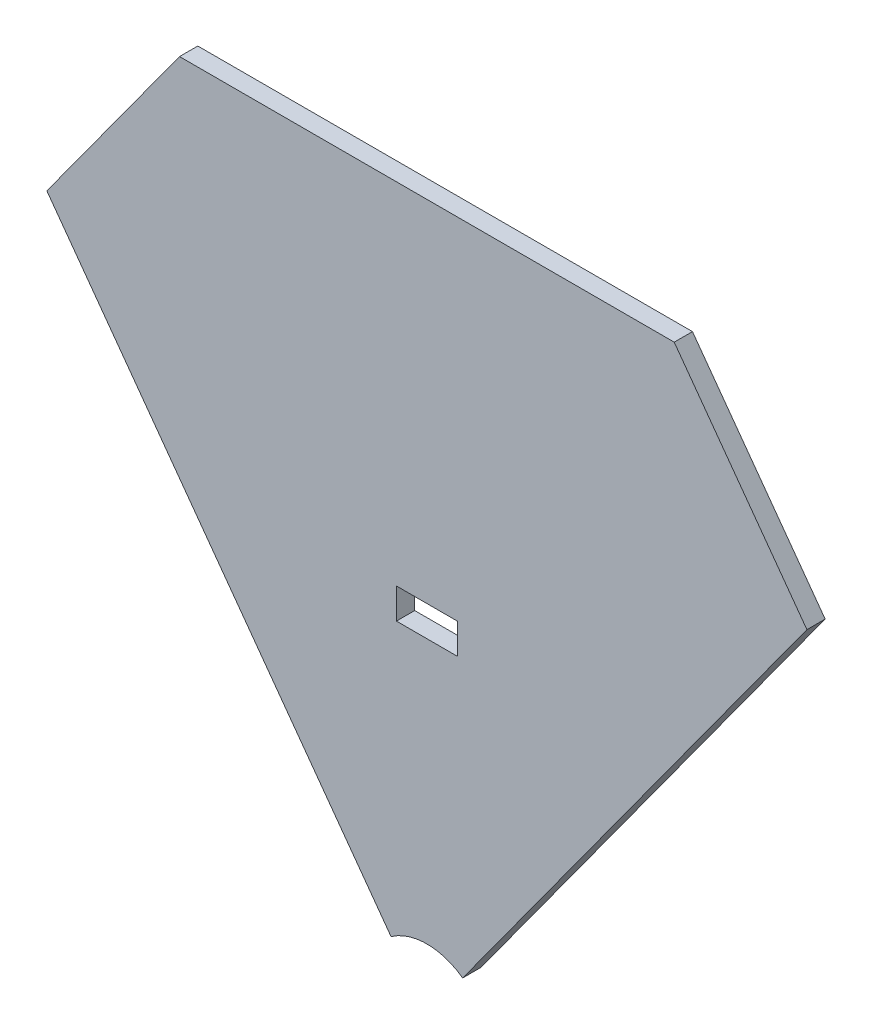
SolidWorks part; units mm, degrees
ref_plane "Front Plane" through (0, 0, 0) normal (0, 0, 1) x (1, 0, 0)
ref_plane "Top Plane" through (0, 0, 0) normal (0, 1, 0) x (1, 0, 0)
ref_plane "Right Plane" through (0, 0, 0) normal (1, 0, 0) x (0, 0, -1)
sketch "Sketch3" plane through (0, 0, 0) normal (0, 0, 1) x (1, 0, 0)
  line L0 (0, 0) -> (73.3263, 100.925)
  line L1 (73.3263, 100.925) -> (-73.3263, 100.925)
  line L2 (-73.3263, 100.925) -> (0, 0)
  line L4 (-5, 58.425) -> (5, 58.425)
  line L5 (-5, 58.425) -> (-5, 53.425)
  line L6 (-5, 53.425) -> (5, 53.425)
  line L7 (5, 58.425) -> (5, 53.425)
  point P5 (0, 100.925)
  point P9 (5, 55.925)
  point P10 (0, 53.425)
  dimension "D1" = 72
  dimension "D2" = 100.925
  dimension "D3" = 10
  dimension "D4" = 5
  dimension "D5" = 45
extrude "Boss-Extrude1" add sketch "Sketch3" along normal blind 3
ref_plane "Offset_R" through (0, 100.925, 0) normal (0, 1, 0) x (1, 0, 0)
sketch "Sketch4" plane through (0, 0, 0) normal (0, 0, -1) x (-1, 0, 0)
  line L0 (-73.3263, 100.925) -> (-84.2244, 115.925)
  line L1 (-84.2244, 115.925) -> (84.2244, 115.925)
  line L2 (84.2244, 115.925) -> (73.3263, 100.925)
  line L3 (73.3263, 100.925) -> (-73.3263, 100.925)
  line L4 (0, 0) -> (-73.3263, 100.925) construction
  line L5 (73.3263, 100.925) -> (0, 0) construction
  dimension "D1" = 15
extrude "Boss-Extrude2" add sketch "Sketch4" against normal up to surface (3 mm away) up to face at (0, 67.2833, 3)
sketch "Sketch5" plane through (0, 0, 3) normal (0, 0, 1) x (1, 0, 0)
  line L0 (-84.2244, 115.925) -> (-40.6319, 115.925)
  line L1 (-84.2244, 115.925) -> (84.2244, 115.925) construction
  line L2 (-40.6319, 115.925) -> (-62.4282, 85.925)
  line L3 (-84.2244, 115.925) -> (0, 0) construction
  line L4 (-62.4282, 85.925) -> (-84.2244, 115.925)
  line L5 (84.2244, 115.925) -> (40.6319, 115.925)
  line L6 (40.6319, 115.925) -> (62.4282, 85.925)
  line L7 (0, 0) -> (84.2244, 115.925) construction
  line L8 (62.4282, 85.925) -> (84.2244, 115.925)
  dimension "D1" = 30
extrude "Cut-Extrude1" cut sketch "Sketch5" against normal through all
ref_axis "Axis1" through (0, 0, 10.9079) along (0, 0, -1)
sketch "Sketch6" plane through (0, 0, 0) normal (0, 0, -1) x (-1, 0, 0)
  circle A0 centre (0, 0) radius 10
extrude "Cut-Extrude2" cut sketch "Sketch6" against normal through all
